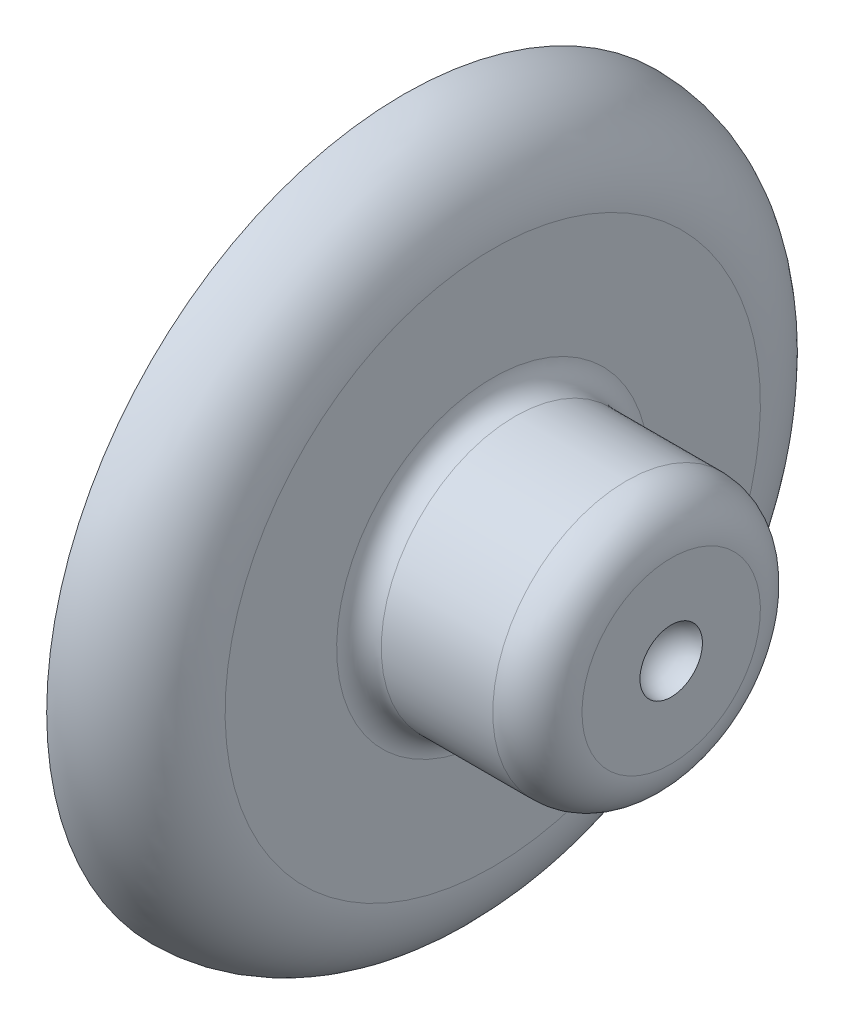
SolidWorks part; units mm, degrees
ref_plane "前视基准面" through (0, 0, 0) normal (0, 0, 1) x (1, 0, 0)
ref_plane "上视基准面" through (0, 0, 0) normal (0, 1, 0) x (1, 0, 0)
ref_plane "右视基准面" through (0, 0, 0) normal (1, 0, 0) x (0, 0, -1)
sketch "草图1" plane through (0, 0, 0) normal (0, 0, 1) x (1, 0, 0)
  line L0 (0, 0) -> (0, 8)
  line L1 (2, 6) -> (2, 3.5)
  line L2 (2.5, 3) -> (5, 3)
  line L3 (6, 2) -> (6, 0.7)
  line L4 (5.3, 0) -> (0, 0)
  line L5 (6, 0) -> (0, 0) construction
  arc A0 (0, 8) -> (2, 6) centre (0, 6) cw
  arc A1 (2, 3.5) -> (2.5, 3) centre (2.5, 3.5) ccw
  arc A2 (5, 3) -> (6, 2) centre (5, 2) cw
  arc A3 (6, 0.7) -> (5.3, 0) centre (6, 0) ccw
revolve "旋转1" add sketch "草图1" angle 360 about L5 reverse direction yes
ref_plane "kapa_to_frame XY" through (0, 0, 0) normal (1, 0, 0) x (0, 0, -1)
ref_plane "kapa_to_frame XZ" through (0, 0, 0) normal (0, -1, 0) x (-1, 0, 0)
ref_plane "kapa_to_frame YZ" through (0, 0, 0) normal (0, 0, -1) x (-1, 0, 0)
ref_axis "kapa_to_frame X" through (0, 0, 80.9) along (0, 0, -1)
ref_axis "kapa_to_frame Y" through (0, -50, 0) along (0, 1, 0)
ref_axis "kapa_to_frame Z" through (80.9, 0, 0) along (-1, 0, 0)
sketch3d "kapa_to_frame"
  point P0 (0, 0, 0)
